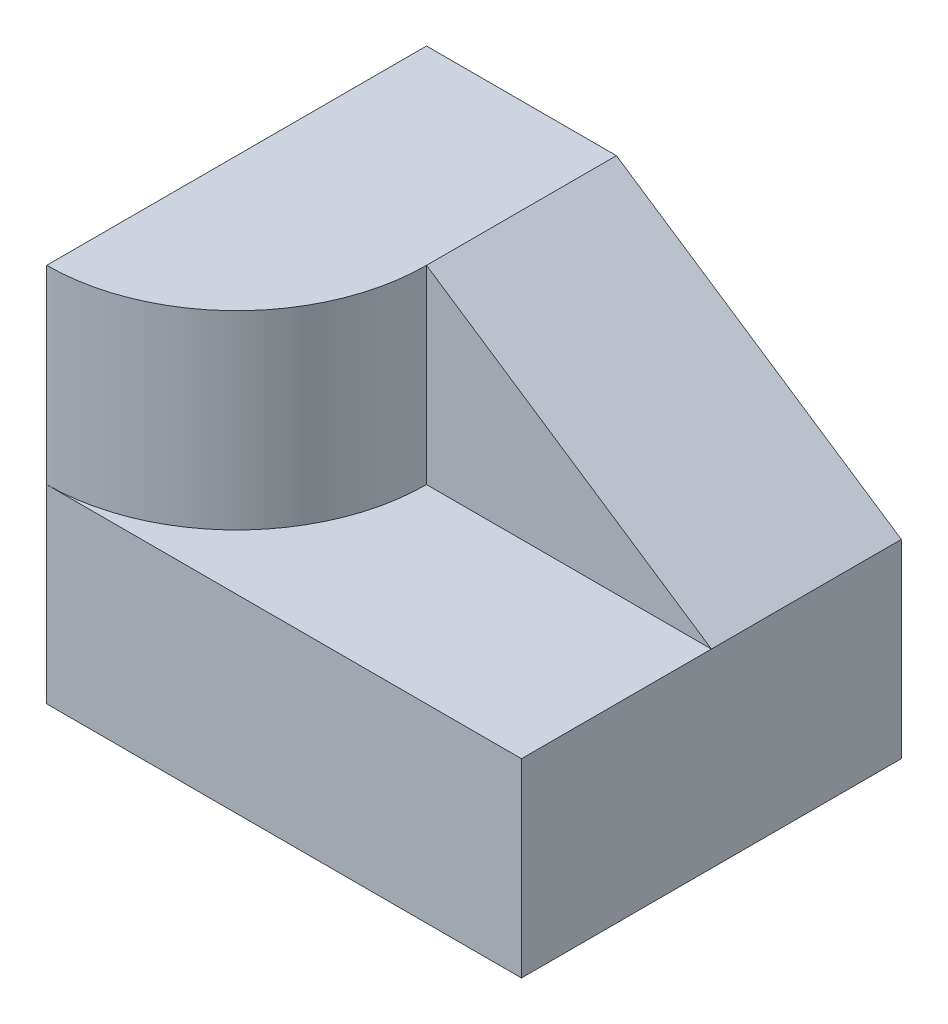
SolidWorks part; units mm, degrees
ref_plane "前基準面" through (0, 0, 0) normal (0, 0, 1) x (1, 0, 0)
ref_plane "上基準面" through (0, 0, 0) normal (0, 1, 0) x (1, 0, 0)
ref_plane "右基準面" through (0, 0, 0) normal (1, 0, 0) x (0, 0, -1)
sketch "草圖1" plane through (0, 0, 0) normal (0, 1, 0) x (1, 0, 0)
  line L1 (-12.5, -10) -> (12.5, -10)
  line L2 (-12.5, -10) -> (-12.5, 10)
  line L3 (-12.5, 10) -> (12.5, 10)
  line L4 (12.5, -10) -> (12.5, 10)
  line L5 (-12.5, -10) -> (12.5, 10) construction
  line L6 (-12.5, 10) -> (12.5, -10) construction
  line L7 (-12.5, 10) -> (-2.5, 10)
  line L8 (-12.5, 10) -> (-12.5, -10)
  line L9 (-12.5, -10) -> (-2.5, -10)
  line L10 (-2.5, 10) -> (-2.5, 0)
  line L11 (12.5, 10) -> (-2.5, 10)
  line L12 (12.5, 10) -> (12.5, 0)
  line L13 (12.5, 0) -> (-2.5, 0)
  line L14 (-2.5, 10) -> (-2.5, 0)
  arc A0 (-2.5, 0) -> (-12.5, -10) centre (-12.5, 0) cw
  point P0 (0, 0)
  dimension "D1" = 20
  dimension "D2" = 25
  dimension "D3" = 10
  dimension "D4" = 10
extrude "填料-伸長1" add sketch "草圖1" along normal blind 10 contours A0 L10 L3 L2 | L13 A0 L1 L4 | L13 L4 L3 L10 region at (3.7817, 0, 5.3462) region at (-7.8325, 0, -0.9335) region at (5, 0, -5)
extrude "填料-伸長2" add sketch "草圖1<3>" along normal blind 20 contours A0 L10 L3 L2 | L13 L4 L3 L10 region at (-7.8325, 0, -0.9335) region at (5, 0, -5)
sketch "草圖1<3>" plane through (0, 0, 0) normal (0, 1, 0) x (1, 0, 0) same geometry as "草圖1"
sketch "草圖2" plane through (0, 0, 0) normal (0, 0, 1) x (1, 0, 0)
  line L0 (-2.5, 20) -> (12.5, 10)
  line L1 (12.5, 10) -> (12.5, 20)
  line L2 (12.5, 20) -> (-2.5, 20)
extrude "除料-伸長1" cut sketch "草圖2" against normal blind 20
scale "縮放比例1" scale about centroid uniform scaling yes scale factor 0.2
